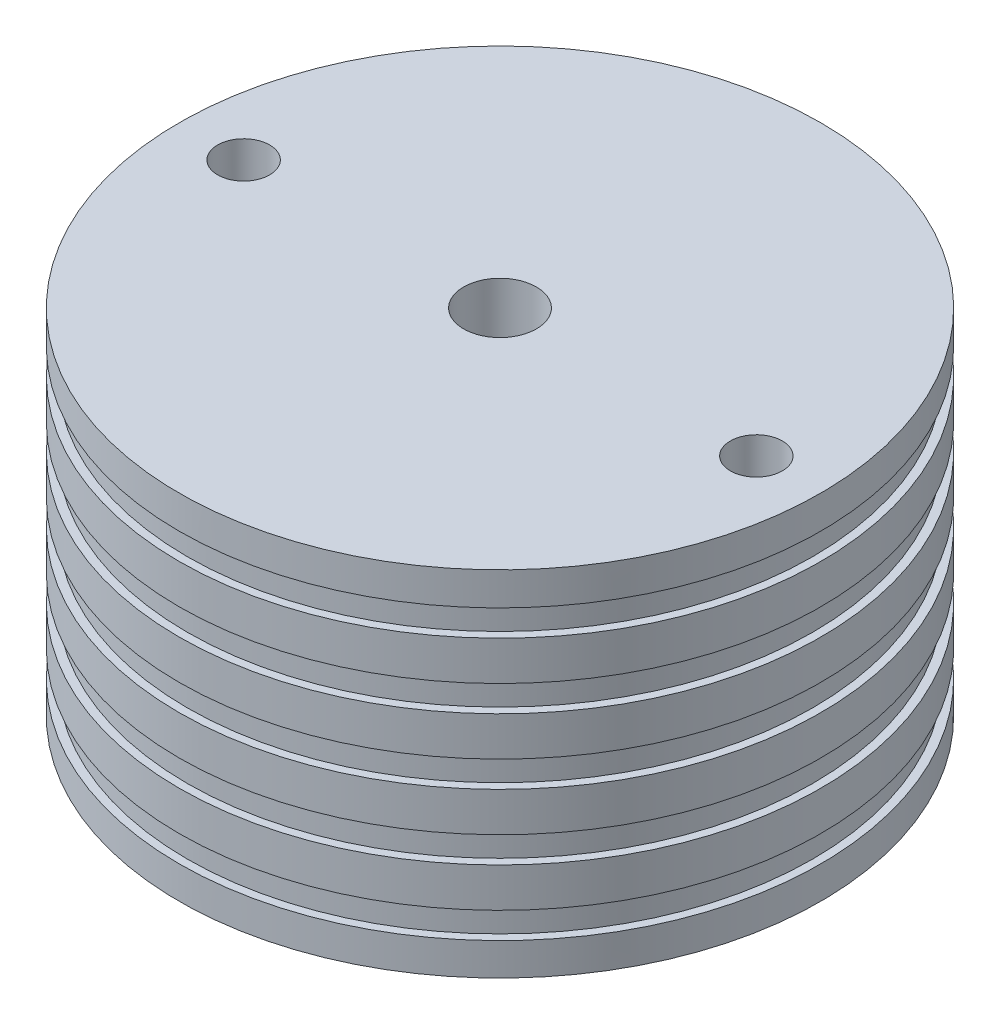
SolidWorks part; units mm, degrees
ref_plane "Front Plane" through (0, 0, 0) normal (0, 0, 1) x (1, 0, 0)
ref_plane "Top Plane" through (0, 0, 0) normal (0, 1, 0) x (1, 0, 0)
ref_plane "Right Plane" through (0, 0, 0) normal (1, 0, 0) x (0, 0, -1)
sketch "Sketch1" plane through (0, 0, 0) normal (0, 0, 1) x (1, 0, 0)
  line L0 (-5.5563, 0) -> (-49, 0)
  line L1 (-49, 0) -> (-49, -54)
  line L2 (-49, -54) -> (-45, -54)
  line L3 (-45, -54) -> (-45, -4)
  line L4 (-45, -4) -> (-10.5563, -4)
  line L5 (-10.5563, -4) -> (-10.5562, -20)
  line L6 (-10.5562, -20) -> (-5.5563, -20)
  line L7 (-5.5563, -20) -> (-5.5563, 0)
  line L8 (-5.5563, 0) -> (0, 0) construction
  line L10 (0, -56.2418) -> (0, 18.81) construction
  point P11 (-8.0562, -20)
  point P14 (-5.5562, -10)
  dimension "D1" = 98
  dimension "D2" = 54
  dimension "D3" = 4
  dimension "D4" = 4
  dimension "D5" = 20
  dimension "D6" = 5
  dimension "D7" = 11.1125
revolve "Revolve1" add sketch "Sketch1" angle 360 about L10
sketch "Sketch2" plane through (0, 0, 0) normal (0, 0, 1) x (1, 0, 0)
  line L0 (0, 0) -> (-49, 0) construction
  line L1 (49, 0) -> (-49, 0) construction
  line L2 (-49, 0) -> (-49, -54) construction
  line L3 (-49, -54) -> (49, -54) construction
  line L4 (-49, -15.0408) -> (-49, -19.0408)
  line L5 (-49, -5.0408) -> (-47.75, -5.0408)
  line L6 (-49, -5.0408) -> (-49, -9.0408)
  line L7 (-49, -9.0408) -> (-47.75, -9.0408)
  line L8 (-47.75, -5.0408) -> (-47.75, -9.0408)
  line L9 (-49, -15.0408) -> (-47.75, -15.0408)
  line L10 (-47.75, -15.0408) -> (-47.75, -19.0408)
  line L11 (-49, -19.0408) -> (-47.75, -19.0408)
  line L12 (-49, -25.0408) -> (-49, -29.0408)
  line L13 (-49, -25.0408) -> (-47.75, -25.0408)
  line L14 (-47.75, -25.0408) -> (-47.75, -29.0408)
  line L15 (-49, -29.0408) -> (-47.75, -29.0408)
  line L16 (-49, -35.0408) -> (-49, -39.0408)
  line L17 (-49, -35.0408) -> (-47.75, -35.0408)
  line L18 (-47.75, -35.0408) -> (-47.75, -39.0408)
  line L19 (-49, -39.0408) -> (-47.75, -39.0408)
  line L20 (-49, -45.0408) -> (-49, -49.0408)
  line L21 (-49, -45.0408) -> (-47.75, -45.0408)
  line L22 (-47.75, -45.0408) -> (-47.75, -49.0408)
  line L23 (-49, -49.0408) -> (-47.75, -49.0408)
  line L24 (0, 0) -> (0, -19.7158) construction
  dimension "D1" = 49
  dimension "D2" = 54
  dimension "D3" = 4
  dimension "D4" = 1.25
  dimension "D5" = 5.0408
  dimension "D6" = 5
revolve "Cut-Revolve1" cut sketch "Sketch2" angle 360 about L24
sketch "Sketch3" plane through (0, -4, 0) normal (0, -1, 0) x (1, 0, 0)
  line L0 (-5.5563, 0) -> (-45, 0)
  line L1 (-2.7781, 4.8119) -> (-22.5, 38.9711)
  line L2 (2.7781, 4.8119) -> (22.5, 38.9711)
  line L3 (5.5563, 0) -> (45, 0)
  line L4 (2.7781, -4.8119) -> (22.5, -38.9711)
  line L5 (-2.7781, -4.8119) -> (-22.5, -38.9711)
  circle A0 centre (0, 0) radius 5.5563 construction
  circle A1 centre (0, 0) radius 45 construction
  circle A2 centre (0, 0) radius 10.5563 construction
  point P18 (0, 0)
  point P23 (0, 0)
  dimension "D2" = 2.7781
  dimension "D1" = 6
extrude "Extrude-Thin1" add sketch "Sketch3" along normal blind 48 thin thin type mid plane wall 4
sketch "Sketch4" plane through (0, 0, 0) normal (0, 0, 1) x (1, 0, 0)
  line L0 (0, 0) -> (-5.5563, 0) construction
  line L1 (0, 0) -> (0, -63.8052) construction
  line L3 (49, 0) -> (-49, 0) construction
  line L4 (5.5563, 0) -> (-5.5563, 0) construction
  line L7 (-5.5563, 0) -> (-10.5563, 0) construction
  line L11 (-10.5563, 0) -> (-10.5563, -5.0408) construction
  line L13 (-49, -5.0408) -> (49, -5.0408) construction
  line L15 (-10.5563, -5.0408) -> (-5.4843, -5.0408) construction
  line L17 (-10.5563, -5.0408) -> (-10.5563, -20)
  line L18 (-10.5563, -20) -> (-5.4843, -20)
  line L24 (-5.4843, -20) -> (-5.5563, -53)
  line L27 (-5.5563, -53) -> (-43.9289, -53)
  arc A0 (-43.9289, -53) -> (-23.1499, -16.1311) centre (6.2684, -57.0009) cw
  arc A2 (-10.5563, -20) -> (-23.1499, -16.1311) centre (-18.0483, -21.9562) ccw
  point P2 (-23.1499, -16.1311)
  dimension "D3" = 50.3565
  dimension "D4" = 7.7432
  dimension "D1" = 5.5563
  dimension "D2" = 5
  dimension "D5" = 6.2684
  dimension "D6" = 18.0483
  dimension "D7" = 5.4843
  dimension "D8" = 23.1499
  dimension "D9" = 43.9289
  dimension "D10" = 16.1311
revolve "Cut-Revolve3" cut sketch "Sketch4" angle 360 about L1 region at (-22.1021, -36.5991, 0)
sketch "Sketch5" plane through (0, -4, 0) normal (0, -1, 0) x (1, 0, 0)
  line L0 (0, 0) -> (0, 19.8661) construction
  line L1 (0, 0) -> (-39.154, 0) construction
  circle A0 centre (-39.154, 0) radius 6.7687
  circle A1 centre (-39.154, 0) radius 3.9687
  circle A2 centre (39.154, 0) radius 3.9687
  circle A3 centre (39.154, 0) radius 6.7687
  dimension "D1" = 2.8
  dimension "D2" = 7.9375
  dimension "D3" = 78.308
extrude "Boss-Extrude1" add sketch "Sketch5" along normal blind 30
extrude "Cut-Extrude1" cut sketch "Sketch5<3>" along normal through all both and the other way through all contours A1 | A1 | A2 region at (-39.154, -4, 0) region at (39.154, -4, 0)
sketch "Sketch5<3>" plane through (0, -4, 0) normal (0, -1, 0) x (1, 0, 0) same geometry as "Sketch5"
fillet "Fillet1" radius 5 28 edges at (-38.5501, -4, -23.2141) (-38.2417, -4, -6.707) (38.5501, -4, -23.2141) (38.2417, -4, -6.707) (38.5501, -4, 23.2141) (38.2417, -4, 6.707) (-38.2417, -4, 6.707) (-38.5501, -4, 23.2141) (-21.5263, -4, -2) (-9.142, -4, -5.2781) (-15.5622, -4, -22.9545) (15.5622, -4, -22.9545) (9.142, -4, -5.2781) (21.5263, -4, -2) (21.5263, -4, 2) (9.142, -4, 5.2781) (15.5622, -4, 22.9545) (-15.5622, -4, 22.9545) (-9.142, -4, 5.2781) (-21.5263, -4, 2) (12.0981, -4, -24.9545) (0, -4, -45) (-12.0981, -4, -24.9545) (0, -4, -10.5563) (-12.0981, -4, 24.9545) (0, -4, 45) (12.0981, -4, 24.9545) (0, -4, 10.5563)
